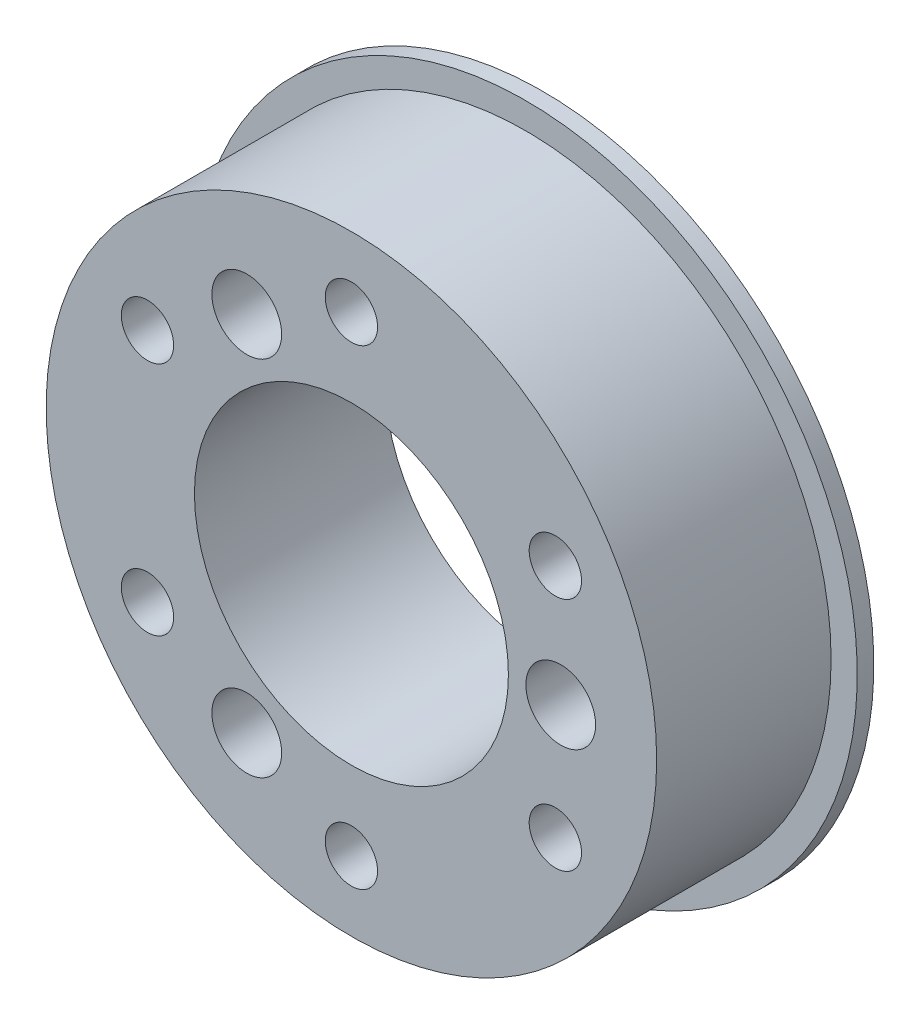
SolidWorks part; units mm, degrees
material "6060 合金"
ref_plane "前视基准面" through (0, 0, 0) normal (0, 0, 1) x (1, 0, 0)
ref_plane "上视基准面" through (0, 0, 0) normal (0, 1, 0) x (1, 0, 0)
ref_plane "右视基准面" through (0, 0, 0) normal (1, 0, 0) x (0, 0, -1)
other "Configuration Table"
sketch "草图1" plane through (0, 0, 0) normal (0, 0, 1) x (1, 0, 0)
  circle A0 centre (0, 0) radius 17.5
  circle A1 centre (0, 0) radius 19
  dimension "D1" = 35
  dimension "D2" = 38
extrude "凸台-拉伸1" add sketch "草图1" along normal blind 10.95 contours A0 region at (0, 0, 0)
extrude "凸台-拉伸2" add sketch "草图1<4>" along normal blind 0.95
sketch "草图1<4>" plane through (0, 0, 0) normal (0, 0, 1) x (1, 0, 0) same geometry as "草图1"
sketch "草图2" plane through (0, 0, 10.95) normal (0, 0, 1) x (1, 0, 0)
  line L0 (0, 0) -> (0, 13.5) construction
  line L1 (0, 0) -> (13.5, 0) construction
  circle A0 centre (0, 0) radius 13.5 construction
  circle A1 centre (0, 0) radius 12 construction
  circle A2 centre (0, 0) radius 9
  circle A3 centre (0, 13.5) radius 1.5
  circle A4 centre (11.6913, 6.75) radius 1.5
  circle A5 centre (11.6913, -6.75) radius 1.5
  circle A6 centre (0, -13.5) radius 1.5
  circle A7 centre (-11.6913, -6.75) radius 1.5
  circle A8 centre (-11.6913, 6.75) radius 1.5
  circle A9 centre (12, 0) radius 2
  circle A10 centre (-6, -10.3923) radius 2
  circle A11 centre (-6, 10.3923) radius 2
  point P20 (0, 0)
  point P27 (0, 0)
  point P34 (0, 0)
  dimension "D1" = 18
  dimension "D2" = 24
  dimension "D3" = 27
  dimension "D4" = 3
  dimension "D6" = 4
  dimension "D5" = 6
  dimension "D7" = 3
extrude "切除-拉伸1" cut sketch "草图2" against normal through all
